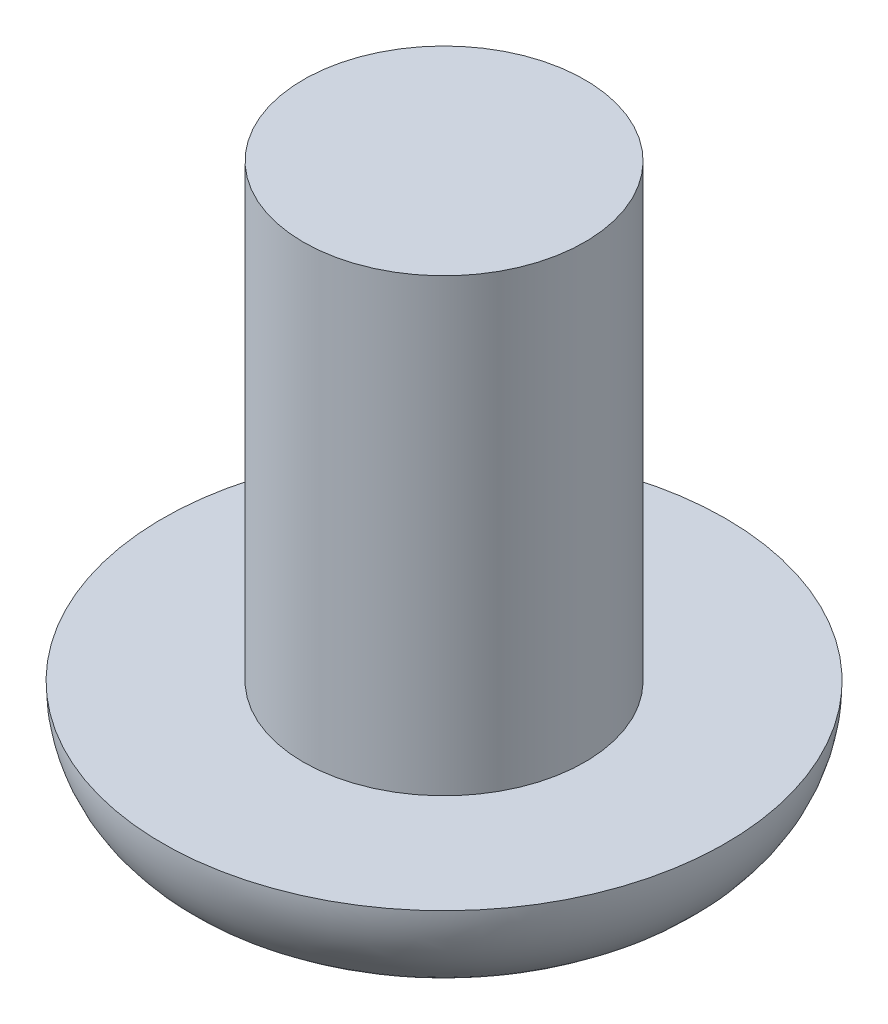
SolidWorks part; units mm, degrees
ref_plane "Front Plane" through (0, 0, 0) normal (0, 0, 1) x (1, 0, 0)
ref_plane "Top Plane" through (0, 0, 0) normal (0, 1, 0) x (1, 0, 0)
ref_plane "Right Plane" through (0, 0, 0) normal (1, 0, 0) x (0, 0, -1)
sketch "Sketch1" plane through (0, 0, 0) normal (0, 1, 0) x (1, 0, 0)
  circle A0 centre (0, 0) radius 2.5
  dimension "D1" = 5
extrude "Boss-Extrude1" add sketch "Sketch1" along normal blind 8 contours A0
sketch "Sketch2" plane through (0, 0, 0) normal (0, -1, 0) x (1, 0, 0)
  circle A0 centre (0, 0) radius 5
  dimension "D1" = 10
extrude "Boss-Extrude2" add sketch "Sketch2" along normal blind 2
fillet "Fillet1" radius 2 1 edges at (0, -2, -5)
